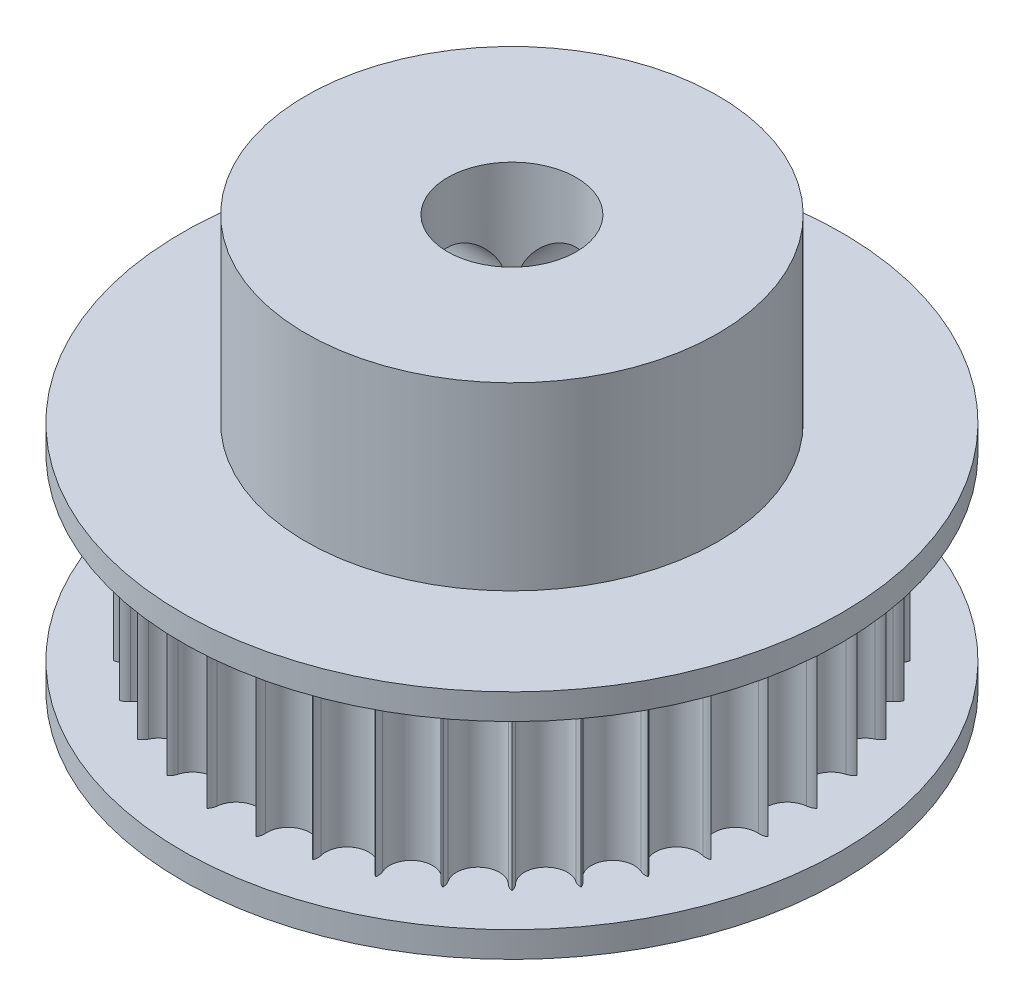
SolidWorks part; units mm, degrees
ref_plane "Front plan" through (0, 0, 0) normal (0, 0, 1) x (1, 0, 0)
ref_plane "Top plan" through (0, 0, 0) normal (0, 1, 0) x (1, 0, 0)
ref_plane "Right plan" through (0, 0, 0) normal (1, 0, 0) x (0, 0, -1)
sketch "Skica2" plane through (0, 0, 0) normal (0, 0, 1) x (1, 0, 0)
  line L0 (8, 8.5) -> (2.5, 8.5)
  line L1 (2.5, 8.5) -> (2.5, -8.5)
  line L2 (2.5, -8.5) -> (6.11, -8.5)
  line L3 (0, -8.5) -> (0, 8.5) construction
  line L4 (0, 8.5) -> (2.5, 8.5)
  line L5 (0, -8.5) -> (2.5, -8.5)
  line L6 (6.11, -8.5) -> (6.11, -7.5)
  line L7 (12.8, 0.5) -> (11.15, 0.5)
  line L8 (11.15, 0.5) -> (11.15, -6.5)
  line L9 (12.8, 0.5) -> (12.8, 1.5)
  line L12 (12.8, -7.5) -> (6.11, -7.5)
  line L13 (12.8, 1.5) -> (8, 1.5)
  line L14 (12.8, -7.5) -> (12.8, -6.5)
  line L15 (11.15, -6.5) -> (12.8, -6.5)
  line L16 (8, 1.5) -> (8, 8.5)
  point P6 (9.455, -7.5)
  point P7 (0, 0)
  dimension "D2" = 1
  dimension "D6" = 25.6
  dimension "D3" = 22.3
  dimension "D1" = 5
  dimension "D8" = 17
  dimension "D4" = 1
  dimension "D7" = 16
  dimension "D9" = 7
revolve "Revolute" add sketch "Skica2" angle 360 about L3 region at (6.3971, -0.6477, 0)
sketch "Sketch2" plane through (0, 0.5, 0) normal (0, -1, 0) x (1, 0, 0)
  line L0 (0, 0) -> (0, 10.7023) construction
  line L1 (0, 0) -> (3.7597, 10.497) construction
  line L3 (0, 0) -> (-2.1589, 10.939) construction
  circle A1 centre (0, 0) radius 9.8663 construction
  circle A2 centre (0, 0) radius 10.65 construction
  arc A3 (-0.8317, 10.6175) -> (0.8317, 10.6175) centre (0, 10.7023) ccw
  arc A7 (-1.3915, 11.0628) -> (-2.1589, 10.939) centre (0, 0) ccw
  arc A8 (0, 12.5893) -> (2.1589, 10.939) centre (0.5977, 11.134) cw
  circle A9 centre (0, 0) radius 11.15 construction
  arc A10 (1.3915, 11.0628) -> (2.1589, 10.939) centre (0, 0) cw
  arc A11 (1.3915, 11.0628) -> (0.8317, 10.6175) centre (1.3291, 10.5667) ccw
  arc A12 (0, 12.5893) -> (-2.1589, 10.939) centre (-0.5977, 11.134) ccw
  arc A13 (-1.3915, 11.0628) -> (-0.8317, 10.6175) centre (-1.3291, 10.5667) cw
  point P0 (0, 0)
  circle M8 centre (0, 0) radius 11.15
  dimension "D2" = 1
  dimension "D4" = 0.836
  dimension "D6" = 22.3
  dimension "D3" = 1.5733
extrude "Cut-Extrude1" cut sketch "Sketch2" along normal up to surface (7 mm away) contours A8 M8 | A11 A3 M8 region at (0, 0.5, 10.6043) region at (0, 0.5, 11.8034) up to face at (12.8, -6.5, 0)
pattern_circular "CirPattern1" count 36 over 360 about axis through (0, -8.5, 0) along (0, -1, 0) of "Cut-Extrude1" reverse direction yes
sketch "Sketch3" plane through (0, 0, 0) normal (1, 0, 0) x (0, 0, -1)
  line L0 (0, 8.5) -> (0, 0.5) construction
  line L1 (2.5, 8.5) -> (-2.5, 8.5) construction
  circle A0 centre (0, 4.5) radius 1.65
  dimension "D1" = 3.3
extrude "Cut-Extrude2" cut sketch "Sketch3" against normal up to next
sketch "Sketch4" plane through (0, 0, 0) normal (0, 0, 1) x (1, 0, 0)
  line L0 (0, 8.5) -> (0, 0.5) construction
  line L1 (12.8, 8.5) -> (-12.8, 8.5) construction
  line L2 (-0.8317, 0.5) -> (0.8317, 0.5) construction
  circle A0 centre (0, 4.5) radius 1.65
  dimension "D1" = 3.3
extrude "Cut-Extrude3" cut sketch "Sketch4" against normal up to next
chamfer "Chamfer1" distance 1 angle 45 1 edges at (6.11, -7.5, 0)
equation "\"`\"=2"
equation "\"D6@Sketch2\"= \"D3@Skica2\""
